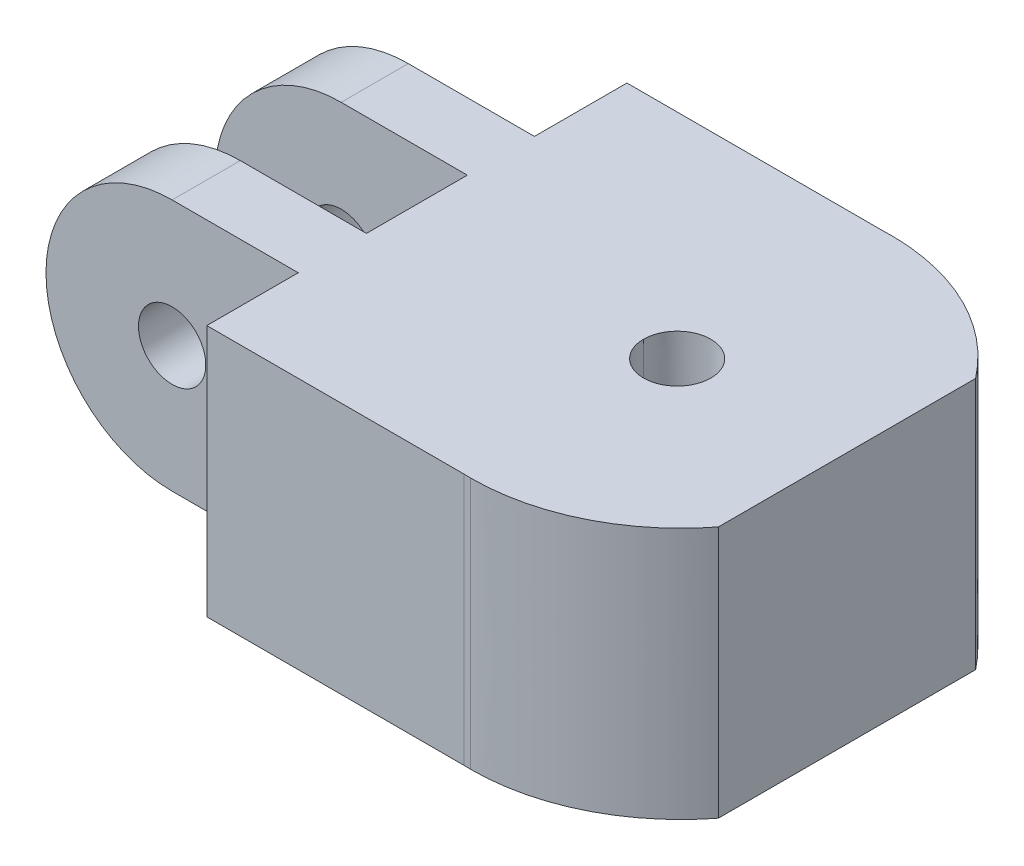
SolidWorks part; units mm, degrees
ref_plane "Front Plane" through (0, 0, 0) normal (0, 0, 1) x (1, 0, 0)
ref_plane "Top Plane" through (0, 0, 0) normal (0, 1, 0) x (1, 0, 0)
ref_plane "Right Plane" through (0, 0, 0) normal (1, 0, 0) x (0, 0, -1)
sketch "Sketch1" plane through (0, 0, 0) normal (0, 1, 0) x (1, 0, 0)
  line L0 (30.2903, 24.9797) -> (14.9999, 24.9797)
  line L1 (14.9999, 24.9797) -> (14.9999, 19.9798)
  line L2 (14.9999, 19.9798) -> (0.6274, 19.9798)
  line L3 (0.6274, 19.9798) -> (0, 19.9798)
  line L4 (0, 19.9798) -> (0, 14.98)
  line L5 (0, 14.98) -> (14.9999, 14.98)
  line L6 (14.9999, 14.98) -> (14.9999, 9.9901)
  line L7 (14.9999, 9.9901) -> (0.6274, 9.9901)
  line L8 (0.6274, 9.9901) -> (0.6274, 9.9384)
  line L9 (0.6274, 9.9384) -> (0, 9.9384)
  line L10 (0, 9.9384) -> (0, 4.9385)
  line L11 (0, 4.9385) -> (14.9999, 4.9385)
  line L12 (14.9999, 4.9385) -> (14.9999, 0)
  line L13 (14.9999, 0) -> (30.2903, 0)
  spline S0 degree 3 poles (28.6856, 12.2814) (28.6856, 13.3859) (29.5813, 14.2813) (30.6858, 14.2813) (31.7903, 14.2813) (32.6857, 13.3859) (32.6857, 12.2814) knots 2 2 2 2 3 3 3 4 4 4 4
  spline S1 degree 3 poles (32.6857, 12.2814) (32.6857, 11.1766) (31.7903, 10.2812) (30.6858, 10.2812) (29.5813, 10.2812) (28.6856, 11.1766) (28.6856, 12.2814) knots 0 0 0 0 1 1 1 2 2 2 2
  spline S2 degree 3 poles (30.6858, 24.9897) (30.5528, 24.9897) (30.4219, 24.9838) (30.2903, 24.9797) knots 0 0 0 0 1 1 1 1
  spline S3 degree 3 poles (30.2903, 0) (30.4219, -0.0041) (30.5528, -0.01) (30.6858, -0.01) knots 15 15 15 15 16 16 16 16
  spline S4 degree 3 poles (30.6858, -0.01) (37.5891, -0.01) (43.1856, 5.5862) (43.1856, 12.4898) knots 16 16 16 16 17 17 17 17
  spline S5 degree 3 poles (43.1856, 12.4898) (43.1856, 19.3935) (37.5891, 24.9897) (30.6858, 24.9897) knots 17 17 17 17 18 18 18 18
extrude "Boss-Extrude1" add sketch "Sketch1" along normal blind 15
fillet "Fillet1" radius 7.5 4 edges at (0, 0, -7.4385) (0, 0, -17.4799) (0, 15, -17.4799) (0, 15, -7.4385)
sketch "Sketch2" plane through (0, 0, -19.9798) normal (0, 0, -1) x (-1, 0, 0)
  circle A0 centre (-7.5, 7.5) radius 2
extrude "Cut-Extrude1" cut sketch "Sketch2" against normal through all
sketch "Sketch3" plane through (0, 0, -19.9798) normal (0, 0, -1) x (-1, 0, 0)
  line L1 (-14.9999, 15) -> (1.7783, 15)
  line L2 (-14.9999, 15) -> (-14.9999, 0)
  line L3 (-14.9999, 0) -> (1.7783, 0)
  line L4 (1.7783, 15) -> (1.7783, 0)
extrude "Cut-Extrude2" cut sketch "Sketch3" against normal blind 0.5
sketch "Sketch4" plane through (0, 0, -4.9385) normal (0, 0, 1) x (1, 0, 0)
  line L1 (14.9999, 15) -> (-2.0698, 15)
  line L2 (14.9999, 15) -> (14.9999, 0)
  line L3 (14.9999, 0) -> (-2.0698, 0)
  line L4 (-2.0698, 15) -> (-2.0698, 0)
extrude "Cut-Extrude3" cut sketch "Sketch4" against normal blind 0.5
sketch "Sketch5" plane through (0, 0, -9.9901) normal (0, 0, -1) x (-1, 0, 0)
  line L1 (-14.9999, 15) -> (7.9687, 15)
  line L2 (-14.9999, 15) -> (-14.9999, -5.5419)
  line L3 (-14.9999, -5.5419) -> (7.9687, -5.5419)
  line L4 (7.9687, 15) -> (7.9687, -5.5419)
extrude "Cut-Extrude4" cut sketch "Sketch5" against normal blind 0.5 and the other way blind 5.5
sketch "Sketch6" plane through (0, 15, 0) normal (0, 1, 0) x (1, 0, 0)
  line L1 (53.2504, 31.1783) -> (40.5766, 31.1783)
  line L2 (53.2504, 31.1783) -> (53.2504, -11.2466)
  line L3 (53.2504, -11.2466) -> (40.5766, -11.2466)
  line L4 (40.5766, 31.1783) -> (40.5766, -11.2466)
extrude "Cut-Extrude5" cut sketch "Sketch6" against normal through all
